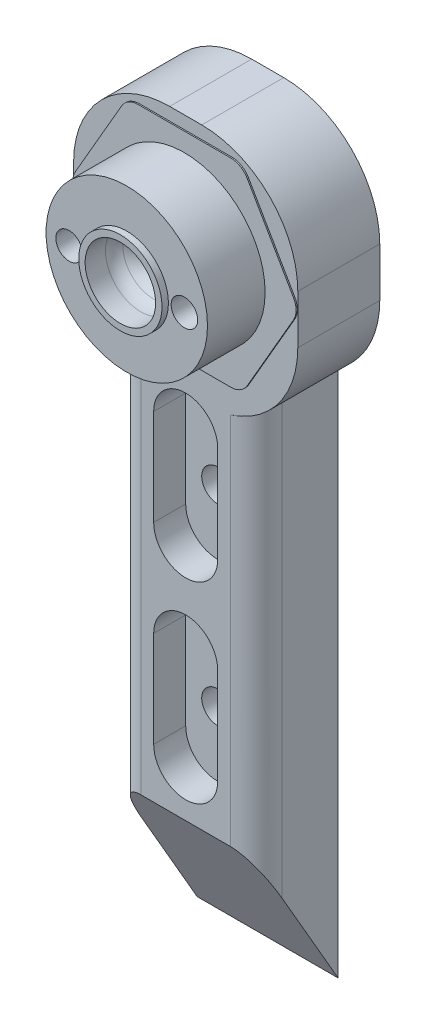
SolidWorks part; units mm, degrees
ref_plane "前视基准面" through (0, 0, 0) normal (0, 0, 1) x (1, 0, 0)
ref_plane "上视基准面" through (0, 0, 0) normal (0, 1, 0) x (1, 0, 0)
ref_plane "右视基准面" through (0, 0, 0) normal (1, 0, 0) x (0, 0, -1)
sketch "草图1" plane through (0, 0, 0) normal (0, 0, 1) x (1, 0, 0)
  circle A0 centre (0, 0) radius 12.6
  dimension "D1" = 25.2
extrude "凸台-拉伸1" add sketch "草图1" along normal blind 9
sketch "草图2" plane through (0, 0, 0) normal (0, 0, -1) x (-1, 0, 0)
  circle A0 centre (0, 0) radius 15
  dimension "D1" = 30
extrude "凸台-拉伸2" add sketch "草图2" along normal blind 5
sketch "草图3" plane through (0, 0, 9) normal (0, 0, 1) x (1, 0, 0)
  circle A0 centre (0, 0) radius 5.5
  dimension "D1" = 11
extrude "切除-拉伸1" cut sketch "草图3" against normal blind 5
sketch "草图4" plane through (0, 0, 9) normal (0, 0, 1) x (1, 0, 0)
  circle A0 centre (-9, 0) radius 2.075
  circle A1 centre (9, 0) radius 2.075
  dimension "D1" = 4.15
  dimension "D2" = 9
  dimension "D3" = 9
extrude "切除-拉伸2" cut sketch "草图4" against normal blind 29
sketch "草图5" plane through (0, 0, 4) normal (0, 0, 1) x (1, 0, 0)
  circle A0 centre (0, 0) radius 3.5
  dimension "D1" = 7
extrude "切除-拉伸3" cut sketch "草图5" against normal blind 31
fillet "圆角1" radius 3 1 edges at (5.5, 0, 4)
fillet "圆角2" radius 5 1 edges at (3.5, 0, 4)
sketch "草图6" plane through (0, 0, 9) normal (0, 0, 1) x (1, 0, 0)
  circle A0 centre (0, 0) radius 5.5
  dimension "D1" = 11
extrude "拉伸-薄壁1" add sketch "草图6" along normal blind 1 thin thin type one direction wall 1
sketch "草图7" plane through (0, 0, -5) normal (0, 0, -1) x (-1, 0, 0)
  line L1 (-8.9489, 15.5) -> (-17.8979, 0)
  line L2 (-17.8979, 0) -> (-8.9489, -15.5)
  line L3 (-8.9489, -15.5) -> (8.9489, -15.5)
  line L4 (8.9489, -15.5) -> (17.8979, 0)
  line L5 (17.8979, 0) -> (8.9489, 15.5)
  line L6 (8.9489, 15.5) -> (-8.9489, 15.5)
  circle A0 centre (0, 0) radius 15.5 construction
  circle A1 centre (0, 0) radius 15
  circle A2 centre (0, 0) radius 15
  dimension "D2" = 31
  dimension "D1" = 0
extrude "凸台-拉伸3" add sketch "草图7" against normal up to surface (5 mm away) up to face at (12.6, 0, 0)
fillet "圆角3" radius 3 6 edges at (17.8979, 0, -2.5) (8.9489, 15.5, -2.5) (-8.9489, 15.5, -2.5) (-17.8979, 0, -2.5) (-8.9489, -15.5, -2.5) (8.9489, -15.5, -2.5)
sketch "草图8" plane through (0, 0, -5) normal (0, 0, -1) x (-1, 0, 0)
  line L6 (-9.815, 14) -> (-17.0318, 1.5)
  line L7 (-17.0318, -1.5) -> (-9.815, -14)
  line L8 (-7.2169, -15.5) -> (7.2169, -15.5)
  line L9 (9.815, -14) -> (17.0318, -1.5)
  line L10 (17.0318, 1.5) -> (9.815, 14)
  line L11 (7.2169, 15.5) -> (-7.2169, 15.5)
  line L12 (-9.815, 14) -> (-17.0318, 1.5)
  line L13 (-17.0318, -1.5) -> (-9.815, -14)
  line L14 (-7.2169, -15.5) -> (7.2169, -15.5)
  line L15 (9.815, -14) -> (17.0318, -1.5)
  line L16 (17.0318, 1.5) -> (9.815, 14)
  line L17 (7.2169, 15.5) -> (-7.2169, 15.5)
  circle A0 centre (0, 0) radius 3.5 construction
  circle A1 centre (0, 0) radius 3.5
  circle A2 centre (-9, 0) radius 4
  circle A3 centre (9, 0) radius 4
  arc A6 (-17.0318, 1.5) -> (-17.0318, -1.5) centre (-14.4338, 0) ccw
  arc A7 (-9.815, -14) -> (-7.2169, -15.5) centre (-7.2169, -12.5) ccw
  arc A8 (7.2169, -15.5) -> (9.815, -14) centre (7.2169, -12.5) ccw
  arc A9 (17.0318, -1.5) -> (17.0318, 1.5) centre (14.4338, 0) ccw
  arc A10 (9.815, 14) -> (7.2169, 15.5) centre (7.2169, 12.5) ccw
  arc A11 (-7.2169, 15.5) -> (-9.815, 14) centre (-7.2169, 12.5) ccw
  arc A12 (-17.0318, 1.5) -> (-17.0318, -1.5) centre (-14.4338, 0) ccw
  arc A13 (-9.815, -14) -> (-7.2169, -15.5) centre (-7.2169, -12.5) ccw
  arc A14 (7.2169, -15.5) -> (9.815, -14) centre (7.2169, -12.5) ccw
  arc A15 (17.0318, -1.5) -> (17.0318, 1.5) centre (14.4338, 0) ccw
  arc A16 (9.815, 14) -> (7.2169, 15.5) centre (7.2169, 12.5) ccw
  arc A17 (-7.2169, 15.5) -> (-9.815, 14) centre (-7.2169, 12.5) ccw
  dimension "D2" = 8
  dimension "D3" = 8
  dimension "D1" = 0
extrude "凸台-拉伸4" add sketch "草图8" along normal blind 8
sketch "草图9" plane through (0, 0, -13) normal (0, 0, -1) x (-1, 0, 0)
  line L1 (-10, 10) -> (10, 10)
  line L2 (-10, 10) -> (-10, -10)
  line L3 (-10, -10) -> (10, -10)
  line L4 (10, 10) -> (10, -10)
  line L5 (-10, 10) -> (10, -10) construction
  line L6 (-10, -10) -> (10, 10) construction
  line L7 (17.5, -17.5) -> (-17.5, -17.5)
  line L8 (17.5, -17.5) -> (17.5, 17.5)
  line L9 (17.5, 17.5) -> (-17.5, 17.5)
  line L10 (-17.5, -17.5) -> (-17.5, 17.5)
  line L11 (17.5, -17.5) -> (-17.5, 17.5) construction
  line L12 (17.5, 17.5) -> (-17.5, -17.5) construction
  point P0 (0, 0)
  point P6 (0, 0)
  dimension "D1" = 20
  dimension "D2" = 20
  dimension "D3" = 35
  dimension "D4" = 35
extrude "凸台-拉伸5" add sketch "草图9" along normal blind 20
sketch "草图10" plane through (0, 0, -13) normal (0, 0, 1) x (1, 0, 0)
  line L4 (17.5, -17.5) -> (17.5, 17.5)
  line L5 (17.5, 17.5) -> (-17.5, 17.5)
  line L6 (-17.5, 17.5) -> (-17.5, -17.5)
  line L7 (-17.5, -17.5) -> (17.5, -17.5)
  line L8 (17.5, -17.5) -> (17.5, 17.5)
  line L9 (17.5, 17.5) -> (-17.5, 17.5)
  line L10 (-17.5, 17.5) -> (-17.5, -17.5)
  line L11 (-17.5, -17.5) -> (17.5, -17.5)
  line L14 (7.2169, 15.5) -> (-7.2169, 15.5)
  line L15 (17.0318, 1.5) -> (9.815, 14)
  line L16 (9.815, -14) -> (17.0318, -1.5)
  line L17 (-7.2169, -15.5) -> (7.2169, -15.5)
  line L18 (-17.0318, -1.5) -> (-9.815, -14)
  line L19 (-9.815, 14) -> (-17.0318, 1.5)
  line L20 (7.2169, 15.5) -> (-7.2169, 15.5)
  line L21 (17.0318, 1.5) -> (9.815, 14)
  line L22 (9.815, -14) -> (17.0318, -1.5)
  line L23 (-7.2169, -15.5) -> (7.2169, -15.5)
  line L24 (-17.0318, -1.5) -> (-9.815, -14)
  line L25 (-9.815, 14) -> (-17.0318, 1.5)
  arc A6 (9.815, 14) -> (7.2169, 15.5) centre (7.2169, 12.5) ccw
  arc A7 (17.0318, -1.5) -> (17.0318, 1.5) centre (14.4338, 0) ccw
  arc A8 (7.2169, -15.5) -> (9.815, -14) centre (7.2169, -12.5) ccw
  arc A9 (-9.815, -14) -> (-7.2169, -15.5) centre (-7.2169, -12.5) ccw
  arc A10 (-17.0318, 1.5) -> (-17.0318, -1.5) centre (-14.4338, 0) ccw
  arc A11 (-7.2169, 15.5) -> (-9.815, 14) centre (-7.2169, 12.5) ccw
  arc A12 (9.815, 14) -> (7.2169, 15.5) centre (7.2169, 12.5) ccw
  arc A13 (17.0318, -1.5) -> (17.0318, 1.5) centre (14.4338, 0) ccw
  arc A14 (7.2169, -15.5) -> (9.815, -14) centre (7.2169, -12.5) ccw
  arc A15 (-9.815, -14) -> (-7.2169, -15.5) centre (-7.2169, -12.5) ccw
  arc A16 (-17.0318, 1.5) -> (-17.0318, -1.5) centre (-14.4338, 0) ccw
  arc A17 (-7.2169, 15.5) -> (-9.815, 14) centre (-7.2169, 12.5) ccw
  dimension "D1" = 0
  dimension "D2" = 0
extrude "凸台-拉伸6" add sketch "草图10" along normal blind 8.5
fillet "圆角4" [suppressed] radius 10
sketch "草图11" plane through (-17.5, 0, 0) normal (-1, 0, 0) x (0, 0, 1)
  line L0 (-33, -17.5) -> (-33, 17.5) construction
  circle A0 centre (-23, 0) radius 2.5
  dimension "D1" = 5
  dimension "D2" = 10
extrude "切除-拉伸4" cut sketch "草图11" against normal blind 15
pattern_circular "阵列(圆周)1" count 4 over 360 about axis through (0, 0, -27) along (0, 0, 1) of "切除-拉伸4"
sketch "草图12" plane through (0, 0, -5) normal (0, 0, -1) x (-1, 0, 0)
  circle A1 centre (9, 0) radius 4
  circle A2 centre (9, 0) radius 4
  circle A3 centre (-9, 0) radius 4
  circle A4 centre (-9, 0) radius 4
  dimension "D1" = 0
  dimension "D2" = 0
extrude "切除-拉伸5" cut sketch "草图12" along normal blind 83
sketch "草图13" plane through (0, 0, -13) normal (0, 0, -1) x (-1, 0, 0)
  line L0 (0, 3.5) -> (0, 10)
  line L1 (10, 10) -> (-10, 10) construction
  line L2 (0, 0) -> (0, 3.5)
  circle A0 centre (0, 0) radius 3.5 construction
extrude "切除-拉伸-薄壁1" [suppressed] cut sketch "草图13" against normal blind 4 thin thin type mid plane wall 4
fillet "圆角5" [suppressed] radius 4
fillet "圆角6" [suppressed] radius 4
fillet "圆角7" [suppressed] radius 3
sketch "草图14" plane through (0, 0, -13) normal (0, 0, -1) x (-1, 0, 0)
  line L0 (-10, -10) -> (10, -10) construction
  line L1 (10, 10) -> (33.2128, 10)
  line L2 (10, 10) -> (10, -10)
  line L3 (10, -10) -> (33.2128, -10)
  line L4 (33.2128, 10) -> (33.2128, -10)
extrude "切除-拉伸6" cut sketch "草图14" along normal blind 41
sketch "草图15" plane through (0, 0, -4.5) normal (0, 0, 1) x (1, 0, 0)
  line L4 (17.5, 17.5) -> (-17.5, 17.5)
  line L5 (-17.5, 17.5) -> (-17.5, -17.5)
  line L6 (-17.5, -17.5) -> (17.5, -17.5)
  line L7 (17.5, -17.5) -> (17.5, 17.5)
  line L8 (17.5, 17.5) -> (-17.5, 17.5)
  line L9 (-17.5, 17.5) -> (-17.5, -17.5)
  line L10 (-17.5, -17.5) -> (17.5, -17.5)
  line L11 (17.5, -17.5) -> (17.5, 17.5)
  line L14 (9.815, -14) -> (17.0318, -1.5)
  line L15 (17.0318, 1.5) -> (9.815, 14)
  line L16 (7.2169, 15.5) -> (-7.2169, 15.5)
  line L17 (-9.815, 14) -> (-17.0318, 1.5)
  line L18 (-17.0318, -1.5) -> (-9.815, -14)
  line L19 (-7.2169, -15.5) -> (7.2169, -15.5)
  line L20 (9.815, -14) -> (17.0318, -1.5)
  line L21 (17.0318, 1.5) -> (9.815, 14)
  line L22 (7.2169, 15.5) -> (-7.2169, 15.5)
  line L23 (-9.815, 14) -> (-17.0318, 1.5)
  line L24 (-17.0318, -1.5) -> (-9.815, -14)
  line L25 (-7.2169, -15.5) -> (7.2169, -15.5)
  arc A14 (17.0318, -1.5) -> (17.0318, 1.5) centre (14.4338, 0) ccw
  arc A15 (9.815, 14) -> (7.2169, 15.5) centre (7.2169, 12.5) ccw
  arc A16 (-7.2169, 15.5) -> (-9.815, 14) centre (-7.2169, 12.5) ccw
  arc A17 (-17.0318, 1.5) -> (-17.0318, -1.5) centre (-14.4338, 0) ccw
  arc A18 (-9.815, -14) -> (-7.2169, -15.5) centre (-7.2169, -12.5) ccw
  arc A19 (7.2169, -15.5) -> (9.815, -14) centre (7.2169, -12.5) ccw
  arc A20 (17.0318, -1.5) -> (17.0318, 1.5) centre (14.4338, 0) ccw
  arc A21 (9.815, 14) -> (7.2169, 15.5) centre (7.2169, 12.5) ccw
  arc A22 (-7.2169, 15.5) -> (-9.815, 14) centre (-7.2169, 12.5) ccw
  arc A23 (-17.0318, 1.5) -> (-17.0318, -1.5) centre (-14.4338, 0) ccw
  arc A24 (-9.815, -14) -> (-7.2169, -15.5) centre (-7.2169, -12.5) ccw
  arc A25 (7.2169, -15.5) -> (9.815, -14) centre (7.2169, -12.5) ccw
  dimension "D1" = 0
  dimension "D2" = 0
extrude "凸台-拉伸7" add sketch "草图15" along normal blind 1.3
sketch "草图16" plane through (0, 0, -13) normal (0, 0, -1) x (-1, 0, 0)
  line L1 (0, 3.5) -> (-9.9868, 3.5)
  line L2 (0, 3.5) -> (0, -3.5)
  line L3 (0, -3.5) -> (-9.9868, -3.5)
  line L4 (-9.9868, 3.5) -> (-9.9868, -3.5)
  circle A0 centre (0, 0) radius 3.5 construction
  dimension "D1" = 7
extrude "切除-拉伸7" [suppressed] cut sketch "草图16" against normal blind 3
sketch "草图18" [suppressed] plane through (0, 0, -13) normal (0, 0, -1) x (-1, 0, 0)
  line L0 (17.1825, 10) -> (-10, 10) construction
  line L1 (7.5, 17.5) -> (30.5, 17.5)
  line L2 (7.5, 17.5) -> (7.5, 10)
  line L3 (7.5, 10) -> (30.5, 10)
  line L4 (30.5, 17.5) -> (30.5, 10)
  dimension "D1" = 7.5
  dimension "D2" = 23
extrude "凸台-拉伸8" [suppressed] add sketch "草图18" along normal blind 20
sketch "草图19" [suppressed] plane through (0, 17.5, 0) normal (0, 1, 0) x (1, 0, 0)
  line L0 (-30.5, 33) -> (7.5, 33) construction
  line L1 (-30.5, 33) -> (-30.5, 13) construction
  circle A0 centre (-22.5, 23) radius 2.55
  dimension "D1" = 5.1
  dimension "D2" = 10
  dimension "D3" = 8
extrude "切除-拉伸8" [suppressed] cut sketch "草图19" against normal blind 20
mirror "镜向1" [suppressed] about plane through (0, 0, 0) normal (0, 1, 0)
fillet "圆角8" [suppressed] radius 3
fillet "圆角9" [suppressed] radius 3
sketch "草图20" plane through (0, 0, -13) normal (0, 0, -1) x (-1, 0, 0)
  line L1 (-25.3768, 23.6724) -> (25.3768, 23.6724)
  line L2 (-25.3768, 23.6724) -> (-25.3768, -23.6724)
  line L3 (-25.3768, -23.6724) -> (25.3768, -23.6724)
  line L4 (25.3768, 23.6724) -> (25.3768, -23.6724)
  line L5 (-25.3768, 23.6724) -> (25.3768, -23.6724) construction
  line L6 (-25.3768, -23.6724) -> (25.3768, 23.6724) construction
  point P0 (0, 0)
extrude "切除-拉伸9" cut sketch "草图20" along normal blind 46
sketch "草图21" plane through (0, 0, -13) normal (0, 0, -1) x (-1, 0, 0)
  line L1 (-17.5, 17.5) -> (17.5, 17.5)
  line L2 (-17.5, 17.5) -> (-17.5, 80)
  line L3 (-17.5, 80) -> (17.5, 80)
  line L4 (17.5, 17.5) -> (17.5, 80)
  dimension "D1" = 35
  dimension "D2" = 62.5
extrude "凸台-拉伸9" add sketch "草图21" against normal up to surface (9.8 mm away) up to face at (0, 0, -3.2)
sketch "草图22" plane through (0, 0, -3.2) normal (0, 0, 1) x (1, 0, 0)
  line L4 (-17.5, 80) -> (-17.5, -17.5)
  line L5 (-17.5, -17.5) -> (17.5, -17.5)
  line L6 (17.5, -17.5) -> (17.5, 80)
  line L7 (17.5, 80) -> (-17.5, 80)
  line L8 (-17.5, 80) -> (-17.5, -17.5)
  line L9 (-17.5, -17.5) -> (17.5, -17.5)
  line L10 (17.5, -17.5) -> (17.5, 80)
  line L11 (17.5, 80) -> (-17.5, 80)
  line L14 (9.815, -14) -> (17.0318, -1.5)
  line L15 (17.0318, 1.5) -> (9.815, 14)
  line L16 (7.2169, 15.5) -> (-7.2169, 15.5)
  line L17 (-9.815, 14) -> (-17.0318, 1.5)
  line L18 (-17.0318, -1.5) -> (-9.815, -14)
  line L19 (-7.2169, -15.5) -> (7.2169, -15.5)
  line L20 (9.815, -14) -> (17.0318, -1.5)
  line L21 (17.0318, 1.5) -> (9.815, 14)
  line L22 (7.2169, 15.5) -> (-7.2169, 15.5)
  line L23 (-9.815, 14) -> (-17.0318, 1.5)
  line L24 (-17.0318, -1.5) -> (-9.815, -14)
  line L25 (-7.2169, -15.5) -> (7.2169, -15.5)
  arc A6 (17.0318, -1.5) -> (17.0318, 1.5) centre (14.4338, 0) ccw
  arc A7 (9.815, 14) -> (7.2169, 15.5) centre (7.2169, 12.5) ccw
  arc A8 (-7.2169, 15.5) -> (-9.815, 14) centre (-7.2169, 12.5) ccw
  arc A9 (-17.0318, 1.5) -> (-17.0318, -1.5) centre (-14.4338, 0) ccw
  arc A10 (-9.815, -14) -> (-7.2169, -15.5) centre (-7.2169, -12.5) ccw
  arc A11 (7.2169, -15.5) -> (9.815, -14) centre (7.2169, -12.5) ccw
  arc A12 (17.0318, -1.5) -> (17.0318, 1.5) centre (14.4338, 0) ccw
  arc A13 (9.815, 14) -> (7.2169, 15.5) centre (7.2169, 12.5) ccw
  arc A14 (-7.2169, 15.5) -> (-9.815, 14) centre (-7.2169, 12.5) ccw
  arc A15 (-17.0318, 1.5) -> (-17.0318, -1.5) centre (-14.4338, 0) ccw
  arc A16 (-9.815, -14) -> (-7.2169, -15.5) centre (-7.2169, -12.5) ccw
  arc A17 (7.2169, -15.5) -> (9.815, -14) centre (7.2169, -12.5) ccw
  dimension "D1" = 0
  dimension "D2" = 0
extrude "凸台-拉伸10" add sketch "草图22" along normal offset from surface (3 mm away) 0.2 up to face at (12.6, 0, 0)
sketch "草图23" plane through (0, 0, -13) normal (0, 0, -1) x (-1, 0, 0)
  line L0 (-17.5, -17.5) -> (17.5, -17.5) construction
  line L1 (-17.5, 80) -> (-11, 80)
  line L2 (-17.5, 80) -> (-17.5, 17.5)
  line L3 (-17.5, 17.5) -> (-11, 17.5)
  line L4 (-11, 80) -> (-11, 17.5)
  line L5 (17.5, 80) -> (11, 80)
  line L6 (17.5, 80) -> (17.5, 17.5)
  line L7 (17.5, 17.5) -> (11, 17.5)
  line L8 (11, 80) -> (11, 17.5)
  dimension "D1" = 22
  dimension "D2" = 35
  dimension "D3" = 35
extrude "切除-拉伸10" cut sketch "草图23" against normal blind 43
fillet "圆角10" radius 15 2 edges at (17.5, -17.5, -6.6) (-17.5, -17.5, -6.6)
fillet "圆角11" radius 15 2 edges at (17.5, 17.5, -6.6) (-17.5, 17.5, -6.6)
sketch "草图24" plane through (0, 0, -0.2) normal (0, 0, 1) x (1, 0, 0)
  line L0 (0, 70) -> (0, 55) construction
  line L1 (5, 70) -> (5, 55)
  line L2 (-5, 70) -> (-5, 55)
  line L3 (0, 40) -> (0, 25) construction
  line L4 (5, 40) -> (5, 25)
  line L5 (-5, 40) -> (-5, 25)
  line L6 (-11, 80) -> (11, 80) construction
  arc A0 (5, 70) -> (-5, 70) centre (0, 70) ccw
  arc A1 (-5, 55) -> (5, 55) centre (0, 55) ccw
  arc A2 (5, 40) -> (-5, 40) centre (0, 40) ccw
  arc A3 (-5, 25) -> (5, 25) centre (0, 25) ccw
  point P3 (0, 62.5)
  point P8 (0, 32.5)
  dimension "D2" = 5
  dimension "D3" = 5
  dimension "D5" = 10
  dimension "D6" = 15
  dimension "D1" = 15
  dimension "D4" = 15
extrude "切除-拉伸11" cut sketch "草图24" against normal blind 5
sketch "草图25" plane through (0, 0, -5.2) normal (0, 0, 1) x (1, 0, 0)
  line L0 (11, 17.5) -> (11, 80) construction
  line L1 (5, 55) -> (5, 70) construction
  line L2 (-11, 80) -> (11, 80) construction
  circle A0 centre (0, 65) radius 2.5
  circle A1 centre (0, 35) radius 2.5
  dimension "D1" = 11
  dimension "D2" = 5
  dimension "D3" = 15
  dimension "D4" = 5
  dimension "D5" = 5
  dimension "D6" = 11
  dimension "D7" = 30
extrude "切除-拉伸12" cut sketch "草图25" against normal blind 33
sketch "草图26" plane through (0, 80, 0) normal (0, 1, 0) x (1, 0, 0)
  line L4 (11, 0.2) -> (11, 13)
  line L5 (11, 13) -> (-11, 13)
  line L6 (-11, 13) -> (-11, 0.2)
  line L7 (-11, 0.2) -> (11, 0.2)
  line L8 (11, 0.2) -> (11, 13)
  line L9 (11, 13) -> (-11, 13)
  line L10 (-11, 13) -> (-11, 0.2)
  line L11 (-11, 0.2) -> (11, 0.2)
  dimension "D1" = 0
extrude "凸台-拉伸11" add sketch "草图26" along normal blind 20
sketch "草图27" plane through (-11, 0, 0) normal (-1, 0, 0) x (0, 0, 1)
  line L0 (-13, 100) -> (-0.2, 77.8297)
  line L1 (-0.2, 100) -> (-0.2, 17.5) construction
  line L2 (-0.2, 77.8297) -> (-0.2, 100)
  line L3 (-0.2, 100) -> (-13, 100)
  dimension "D1" = 30
extrude "切除-拉伸13" cut sketch "草图27" against normal up to vertex (22 mm away) up to point (11, 17.5, -0.2)
sketch "草图28" plane through (0, 0, -13) normal (0, 0, -1) x (-1, 0, 0)
  line L0 (7, 90) -> (7, 10)
  line L1 (11, 100) -> (11, 17.5) construction
  line L2 (-11, 100) -> (11, 100) construction
  dimension "D1" = 4
  dimension "D2" = 10
  dimension "D3" = 80
sweep "切除-扫描1" cut path "草图28" circular profile diameter 6 parameters "D3"=6
fillet "圆角13" radius 3 1 edges at (-7, 10, -10)
fillet "圆角14" radius 3 1 edges at (-7, 90, -10)
fillet "圆角15" radius 4 2 edges at (-11, 47.6649, -0.2) (11, 47.6649, -0.2)
mirror "镜向2" about plane through (-17.5, -17.5, -33) normal (0, 1, 0) of bodies 134
delete or keep bodies "实体-删除/保留 1" type delete bodies bodies 134
